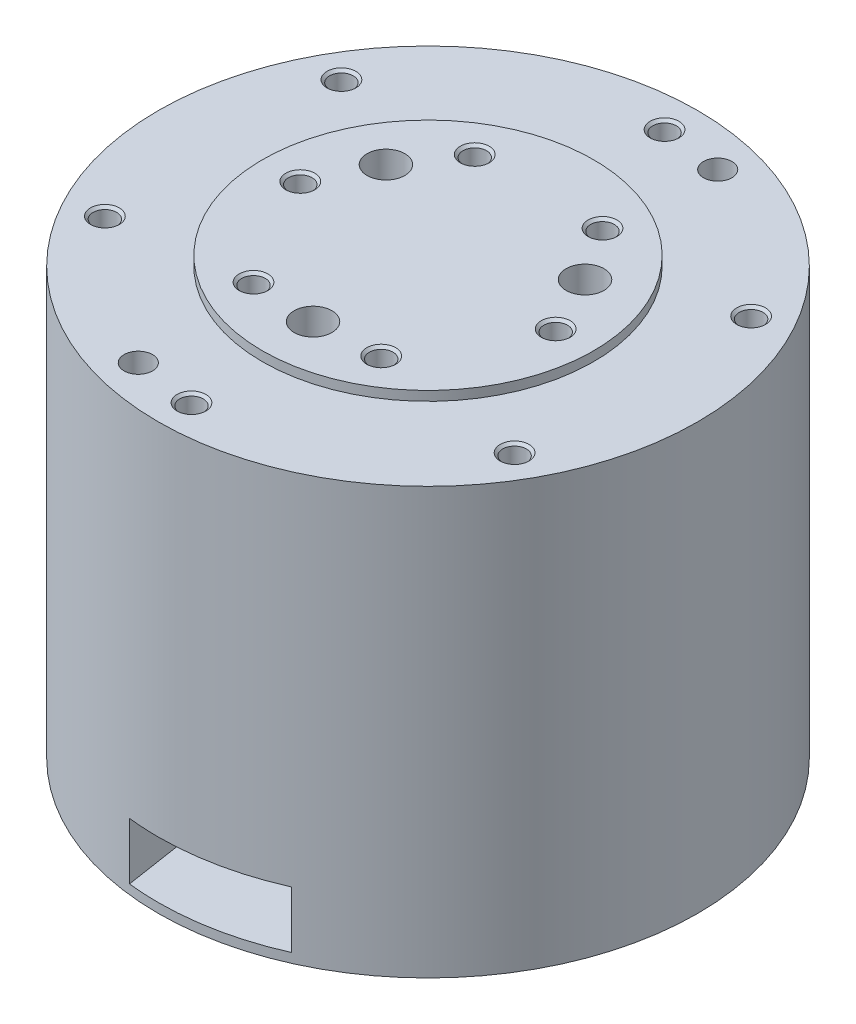
SolidWorks part; units mm, degrees
material "1060 合金"
ref_plane "前视基准面" through (0, 0, 0) normal (0, 0, 1) x (1, 0, 0)
ref_plane "上视基准面" through (0, 0, 0) normal (0, 1, 0) x (1, 0, 0)
ref_plane "右视基准面" through (0, 0, 0) normal (1, 0, 0) x (0, 0, -1)
sketch "草图1" plane through (0, 0, 0) normal (0, 1, 0) x (1, 0, 0)
  circle A0 centre (0, 0) radius 28.5
  dimension "D1" = 57
extrude "凸台-拉伸1" add sketch "草图1" along normal blind 45
sketch "草图2" plane through (0, 45, 0) normal (0, 1, 0) x (1, 0, 0)
  circle A0 centre (0, 0) radius 17.5
  dimension "D1" = 35
extrude "凸台-拉伸2" add sketch "草图2" along normal blind 1 and the other way blind 30
sketch "草图11" plane through (0, 45, 0) normal (0, 1, 0) x (1, 0, 0)
  line L0 (0, 0) -> (40.3218, 0) construction
  line L1 (0, 0) -> (0, 43.0284) construction
  line L3 (9.681, 36.1301) -> (-8.6354, -32.2279) construction
  circle A0 centre (0, 0) radius 25 construction
  circle A1 centre (6.4705, 24.1481) radius 1.5
  circle A2 centre (-6.4705, -24.1481) radius 1.5
  point P9 (0, 25)
  point P27 (0, 0)
  dimension "D1" = 50
  dimension "D3" = 3
  dimension "D2" = 15
  dimension "D4" = 2
hole_wizard "M3 螺纹孔2" positions "草图11" profile "草图12" tap size "M3" standard "GB"
sketch "草图12" plane through (0, 45, -25) normal (1, 0, 0) x (0, 0, 1)
  line L0 (0, 0) -> (0, 5.7511)
  line L1 (0, 5.7511) -> (1.25, 5)
  line L2 (1.25, 5) -> (1.25, 0.275)
  line L3 (1.25, 0.275) -> (1.525, 0)
  line L5 (1.525, 0) -> (0, 0)
  line L6 (-1.25, 0.275) -> (-1.525, 0) construction
  line L10 (0, 5.7511) -> (-1.25, 5) construction
  line L11 (0, -6.35) -> (0, 107.95) construction
  dimension "螺纹孔钻头直径" = 2.5
  dimension "螺纹孔钻头深度" = 5
  dimension "近端锥形沉头孔直径" = 3.05
  dimension "近端锥形沉头孔角度" = 90
  dimension "导头角度" = 118
cosmetic thread "孔螺纹线2" parameters "D1"=4.5, "D2"=3
ref_axis "基准轴2" through (0, 0, 0) along (0, -1, 0)
pattern_circular "阵列(圆周)2" count 6 over 360 about axis through (0, 0, 0) along (0, -1, 0) of "M3 螺纹孔2"
extrude "切除-拉伸1" cut sketch "草图11<2>" against normal blind 5
sketch "草图11<2>" plane through (0, 45, 0) normal (0, 1, 0) x (1, 0, 0) same geometry as "草图11"
sketch "草图13" plane through (0, 46, 0) normal (0, 1, 0) x (1, 0, 0)
  circle A0 centre (0, 0) radius 13.5 construction
  circle A1 centre (0, 0) radius 12.15 construction
  circle A2 centre (0, -12.15) radius 2
  circle A3 centre (-10.5222, 6.075) radius 2
  circle A4 centre (10.5222, 6.075) radius 2
  point P11 (-13.5, 0)
  dimension "D1" = 27
  dimension "D2" = 24.3
  dimension "D3" = 4
  dimension "D4" = 3
hole_wizard "M3 螺纹孔3" positions "草图13" profile "草图14" tap size "M3" standard "GB"
sketch "草图14" plane through (-13.5, 46, 0) normal (1, 0, 0) x (0, 0, 1)
  line L0 (0, 0) -> (0, 5.7511)
  line L1 (0, 5.7511) -> (1.25, 5)
  line L2 (1.25, 5) -> (1.25, 0.275)
  line L3 (1.25, 0.275) -> (1.525, 0)
  line L5 (1.525, 0) -> (0, 0)
  line L6 (-1.25, 0.275) -> (-1.525, 0) construction
  line L10 (0, 5.7511) -> (-1.25, 5) construction
  line L11 (0, -6.35) -> (0, 107.95) construction
  dimension "螺纹孔钻头直径" = 2.5
  dimension "螺纹孔钻头深度" = 5
  dimension "近端锥形沉头孔直径" = 3.05
  dimension "近端锥形沉头孔角度" = 90
  dimension "导头角度" = 118
cosmetic thread "孔螺纹线3" parameters "D1"=4.5, "D2"=3
pattern_circular "阵列(圆周)3" count 6 over 360 about axis through (0, 45, 0) along (0, -1, 0) of "M3 螺纹孔3"
extrude "切除-拉伸2" cut sketch "草图13<2>" against normal blind 4 contours A2 | A4 | A3
sketch "草图13<2>" plane through (0, 46, 0) normal (0, 1, 0) x (1, 0, 0) same geometry as "草图13"
sketch "草图16" plane through (0, 0, 0) normal (0, -1, 0) x (-1, 0, 0)
  line L0 (0, 0) -> (-38.2553, 0) construction
  line L2 (-13.435, -13.435) -> (0, 0) construction
  circle A0 centre (0, 0) radius 19 construction
  point P5 (-13.435, -13.435)
  point P15 (0, 0)
  point P16 (-13.435, -13.435)
  dimension "D1" = 38
  dimension "D2" = 45
hole_wizard "M3 螺纹孔4" positions "草图16" profile "草图17" tap size "M3" standard "GB"
sketch "草图17" plane through (13.435, 0, 13.435) normal (1, 0, 0) x (0, 0, -1)
  line L0 (0, 0) -> (0, 4.7511)
  line L1 (0, 4.7511) -> (1.25, 4)
  line L2 (1.25, 4) -> (1.25, 0.275)
  line L3 (1.25, 0.275) -> (1.525, 0)
  line L5 (1.525, 0) -> (0, 0)
  line L6 (-1.25, 0.275) -> (-1.525, 0) construction
  line L10 (0, 4.7511) -> (-1.25, 4) construction
  line L11 (0, -6.35) -> (0, 107.95) construction
  dimension "螺纹孔钻头直径" = 2.5
  dimension "螺纹孔钻头深度" = 4
  dimension "近端锥形沉头孔直径" = 3.05
  dimension "近端锥形沉头孔角度" = 90
  dimension "导头角度" = 118
cosmetic thread "孔螺纹线4" parameters "D1"=4.5, "D2"=3
ref_axis "基准轴4" through (0, 45, 0) along (0, -1, 0)
pattern_circular "阵列(圆周)4" count 4 over 360 about axis through (0, 45, 0) along (0, -1, 0) of "M3 螺纹孔4"
sketch "草图18" plane through (0, 0, 0) normal (0, -1, 0) x (1, 0, 0)
  line L0 (-13.435, -13.435) -> (13.435, -13.435) construction
  line L1 (0, -13.435) -> (0, -31.9001) construction
  line L2 (-7.5, -18.5) -> (7.5, -18.5)
  line L3 (7.5, -18.5) -> (7.5, -28.5)
  line L4 (7.5, -28.5) -> (-7.5, -28.5)
  line L5 (-7.5, -28.5) -> (-7.5, -18.5)
  line L6 (11.7484, 27.0273) -> (10.2271, 17.1437)
  line L7 (10.2271, 17.1437) -> (-4.5983, 19.4256)
  line L8 (-4.5983, 19.4256) -> (-3.077, 29.3092)
  line L9 (-3.077, 29.3092) -> (11.7484, 27.0273)
  circle A0 centre (0, 0) radius 28.5 construction
  point P18 (0, 0)
  dimension "D1" = 15
  dimension "D2" = 10
  dimension "D3" = 2
extrude "切除-拉伸3" cut sketch "草图18" against normal blind 6 from offset 1 offset against normal yes
